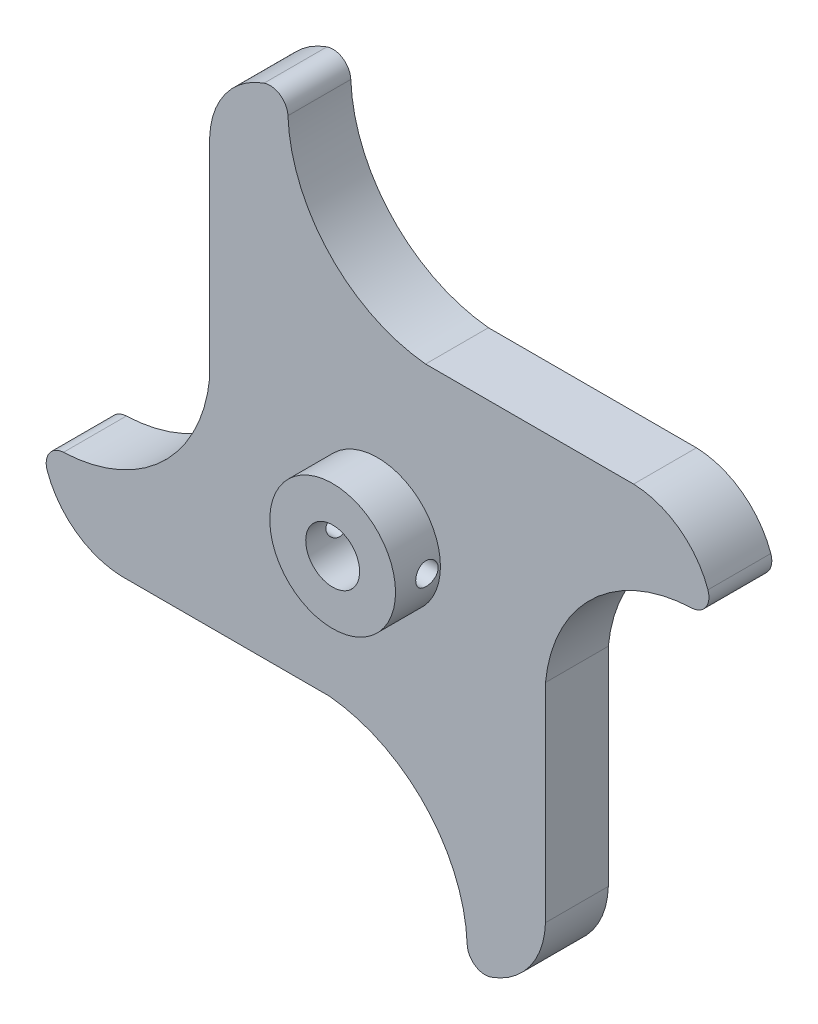
SolidWorks part; units mm, degrees
ref_plane "前视基准面" through (0, 0, 0) normal (0, 0, 1) x (1, 0, 0)
ref_plane "上视基准面" through (0, 0, 0) normal (0, 1, 0) x (1, 0, 0)
ref_plane "右视基准面" through (0, 0, 0) normal (1, 0, 0) x (0, 0, -1)
sketch "草图1" plane through (0, 0, 0) normal (0, 0, 1) x (1, 0, 0)
  circle A0 centre (0, 0) radius 3
  arc A5 (40.8798, 28.7896) -> (28.7896, 40.8798) centre (0, 0) ccw
  arc A7 (-28.7896, 40.8798) -> (-40.8798, 28.7896) centre (0, 0) ccw
  arc A9 (-40.8798, -28.7896) -> (-28.7896, -40.8798) centre (0, 0) ccw
  arc A11 (28.7896, -40.8798) -> (40.8798, -28.7896) centre (0, 0) ccw
  arc A13 (-22.8945, 32.8) -> (22.8945, 32.8) centre (0, 55.6945) ccw
  arc A14 (32.8, 22.8945) -> (32.8, -22.8945) centre (55.6945, 0) ccw
  arc A15 (22.8945, -32.8) -> (-22.8945, -32.8) centre (0, -55.6945) ccw
  arc A16 (-32.8, -22.8945) -> (-32.8, 22.8945) centre (-55.6945, 0) ccw
  arc A21 (-28.7896, 40.8798) -> (28.7896, 40.8798) centre (0, 55.6945) ccw
  arc A22 (40.8798, 28.7896) -> (40.8798, -28.7896) centre (55.6945, 0) ccw
  arc A23 (28.7896, -40.8798) -> (-28.7896, -40.8798) centre (0, -55.6945) ccw
  arc A24 (-40.8798, -28.7896) -> (-40.8798, 28.7896) centre (-55.6945, 0) ccw
  point P13 (45, 0)
  point P16 (0, 0)
  point P45 (0, 0)
  point P47 (0, 0)
  point P63 (0, 0)
  dimension "D3" = 4
  dimension "D4" = 4
extrude "凸台-拉伸1" add sketch "草图1" along normal blind 7 contours A24 A16 A9 A23 A15 A11 A22 A14 A5 A21 A13 A7 A0 region at (35.9294, 27.09, 0)
sketch "草图2" plane through (0, 0, 7) normal (0, 0, 1) x (1, 0, 0)
  line L0 (24.2343, 0) -> (24.2343, 20.8516)
  line L1 (0, -24.2343) -> (-200, -24.2343)
  line L2 (-200, -71.6) -> (3.2733, -71.6)
  line L3 (0, -70) -> (-200, -70)
  line L4 (-200, -23.4) -> (-200, -71.6)
  line L5 (24.2343, 34.0432) -> (24.2343, 20.8516)
  line L6 (-200, -47.5) -> (-20.9464, -47.5)
  line L7 (-200, -23.4) -> (-42.5285, -23.4)
  line L8 (70, 0) -> (70, 107.3223)
  line L9 (24.2343, 34.0432) -> (24.2343, 107.3223)
  line L10 (-35.8334, -17.6395) -> (24.2343, 34.0432)
  line L11 (24.2343, 34.0432) -> (-43.4982, -24.2343)
  line L12 (0, -24.2343) -> (0, 0)
  line L13 (0, 0) -> (0, -24.2343)
  line L14 (-43.4982, -24.2343) -> (-43.4982, -70)
  line L15 (-310.8913, -229.5208) -> (-198.8913, -229.5208)
  line L16 (-254.8913, -229.5208) -> (-251.3913, -229.5208)
  line L17 (-251.3913, -229.5208) -> (-258.3913, -229.5208)
  line L18 (-258.3913, -229.5208) -> (-258.3913, -112.5315)
  line L19 (-258.3913, -112.5315) -> (-251.3913, -112.5315)
  line L20 (-251.3913, -112.5315) -> (-251.3913, -229.5208)
  line L21 (24.2343, 107.3223) -> (70, 107.3223)
  line L22 (47.1172, 107.3223) -> (47.1172, -141.393)
  line L23 (-20.9464, -47.5) -> (114.3656, -47.5)
  line L24 (0, 0) -> (0, -24.2343)
  circle A0 centre (0, -49) radius 21
  circle A1 centre (-310.8913, -229.5208) radius 38.25
  arc A2 (0, -24.2343) -> (24.2343, 0) centre (0, 0) ccw
  arc A3 (0, -70) -> (70, 0) centre (0, 0) ccw
  circle A4 centre (-198.8913, -229.5208) radius 38.25
  circle A5 centre (0, 0) radius 47.1172
  circle A10 centre (-254.8913, -208.9571) radius 21.4063
  point P19 (0, 0)
sketch "草图5" plane through (0, 0, 7) normal (0, 0, 1) x (1, 0, 0)
  line L1 (0, 2.5) -> (-1.7806, 2.5)
  line L2 (-1.7806, 2.5) -> (1.6583, 2.5)
  arc A0 (1.6583, 2.5) -> (-1.6583, 2.5) centre (0, 0) ccw
  circle A1 centre (0, 0) radius 7
  circle M18 centre (0, 0) radius 3
extrude "凸台-拉伸2" add sketch "草图5" along normal blind 4 contours A1 M18 | L1 L2 M18 region at (0, 2.7015, 7) region at (-6.802, 0, 7)
sketch "草图10" plane through (0, 0, 7) normal (0, 0, -1) x (-1, 0, 0)
  line L0 (-1.6583, 2.5) -> (1.6583, 2.5) construction
  line L1 (-1.6583, 2.5) -> (1.6583, 2.5)
  arc A0 (-1.6583, 2.5) -> (1.6583, 2.5) centre (0, 0) cw
  arc A1 (1.6583, 2.5) -> (-1.6583, 2.5) centre (0, 0) ccw construction
extrude "凸台-拉伸3" add sketch "草图10" along normal up to surface (7 mm away) up to face at (0, 0, 0)
sketch "草图11" plane through (0, 0, 0) normal (1, 0, 0) x (0, 0, -1)
  line L0 (0, 0) -> (-7, 0)
  line L1 (-7, 0) -> (-10, 0)
  circle A0 centre (-8.5, 0) radius 1.25
extrude "切除-拉伸5" cut sketch "草图11" against normal blind 15 and the other way blind 8 contours L1 A0 | L1 A0 region at (0, -0.5305, 8.5) region at (0, 0.5305, 8.5)
sketch "草图12" plane through (0, 0, 11) normal (0, 0, 1) x (1, 0, 0)
  circle A0 centre (0, 0) radius 6
  circle A1 centre (0, 0) radius 3
extrude "凸台-拉伸4" add sketch "草图12" along normal blind 1
sketch "草图13" plane through (0, 0, 0) normal (0, 0, -1) x (-1, 0, 0)
  arc A0 (-25.2436, 31.0284) -> (25.2436, 31.0284) centre (0, 50.6945) ccw
  arc A1 (31.0284, 25.2436) -> (31.0284, -25.2436) centre (50.6945, 0) ccw
  arc A2 (25.2436, -31.0284) -> (-25.2436, -31.0284) centre (0, -50.6945) ccw
  arc A3 (-31.0284, -25.2436) -> (-31.0284, 25.2436) centre (-50.6945, 0) ccw
  arc A4 (-25.2436, 31.0284) -> (-31.0284, 25.2436) centre (0, 0) ccw
  circle A5 centre (0, 0) radius 82.6945
  arc A6 (-31.0284, -25.2436) -> (-25.2436, -31.0284) centre (0, 0) ccw
  arc A7 (25.2436, -31.0284) -> (31.0284, -25.2436) centre (0, 0) ccw
  arc A8 (31.0284, 25.2436) -> (25.2436, 31.0284) centre (0, 0) ccw
  point P14 (0, 0)
  dimension "D1" = 4
extrude "切除-拉伸13" cut sketch "草图13" against normal blind 10
fillet "圆角1" radius 2 4 edges at (-31.0284, -25.2436, 3.5) (31.0284, -25.2436, 3.5) (25.2436, 31.0284, 3.5) (-31.0284, 25.2436, 3.5)
fillet "圆角2" radius 2 4 edges at (-25.2436, -31.0284, 3.5) (25.2436, -31.0284, 3.5) (31.0284, 25.2436, 3.5) (-25.2436, 31.0284, 3.5)
sketch "草图14" plane through (0, 0, 0) normal (0, 0, -1) x (-1, 0, 0)
  line L0 (0, 18.6945) -> (-34.0956, 18.6945)
  line L1 (18.6945, 0) -> (18.6945, 34.0956)
  line L2 (0, -18.6945) -> (34.0956, -18.6945)
  line L3 (-18.6945, 0) -> (-18.6945, -34.0956)
  line L4 (34.0956, -16.9082) -> (34.0956, -18.6945)
  line L5 (-16.9082, -34.0956) -> (-18.6945, -34.0956)
  line L6 (-34.0956, 16.9082) -> (-34.0956, 18.6945)
  line L7 (16.9082, 34.0956) -> (18.6945, 34.0956)
  line L8 (13.8017, 34.0956) -> (18.6945, 34.0956)
  line L9 (34.0956, -13.8017) -> (34.0956, -18.6945)
  line L10 (-13.8017, -34.0956) -> (-18.6945, -34.0956)
  line L11 (-34.0956, 13.8017) -> (-34.0956, 18.6945)
  arc A1 (-23.9852, 29.5117) -> (23.9852, 29.5117) centre (0, 50.6945) ccw construction
  arc A5 (0, 18.6945) -> (13.8017, 34.0956) centre (-0.7997, 33.296) ccw
  arc A6 (18.6945, 0) -> (34.0956, -13.8017) centre (33.296, 0.7997) ccw
  arc A7 (0, -18.6945) -> (-13.8017, -34.0956) centre (0.7997, -33.296) ccw
  arc A8 (-18.6945, 0) -> (-34.0956, 13.8017) centre (-33.296, -0.7997) ccw
  point P22 (0, 0)
  point P29 (0, 0)
  point P35 (0, 0)
  point P41 (0, 0)
  arc M1 (-23.9852, -29.5117) -> (23.9852, -29.5117) centre (0, -50.6945) cw
  arc M5 (29.5117, -23.9852) -> (29.5117, 23.9852) centre (50.6945, 0) cw
  arc M9 (23.9852, 29.5117) -> (-23.9852, 29.5117) centre (0, 50.6945) cw
  arc M13 (-29.5117, 23.9852) -> (-29.5117, -23.9852) centre (-50.6945, 0) cw
  arc M17 (1.6583, 2.5) -> (-1.6583, 2.5) centre (0, 0) cw
  line M18 (-1.6583, 2.5) -> (1.6583, 2.5)
  dimension "D1" = 4
  dimension "D3" = 4
  dimension "D2" = 4
  dimension "D4" = 4
extrude "凸台-拉伸5" add sketch "草图14" against normal up to surface (7 mm away) contours L3 L2 L1 L0 M13 M1 M5 M9 M18 M17 | A8 L0 L6 L11 M13 | A5 L1 L7 L8 M9 | A6 L2 L4 L9 M5 | A7 L3 L5 L10 M1 region at (-10.0359, 19.5734, 0) region at (-14.1137, 26.53, 0) region at (26.53, 14.1137, 0) region at (-26.53, -14.1137, 0) region at (14.1137, -26.53, 0) up to face at (0, 0, 7)
sketch "草图15" plane through (0, 0, 0) normal (0, 0, -1) x (-1, 0, 0)
  line L0 (-24.7231, 18.6945) -> (0, 18.6945)
  line L1 (18.6945, 0) -> (18.6945, 24.7231)
  line L2 (24.7231, -18.6945) -> (0.9271, -18.708)
  line L3 (24.7231, -18.6945) -> (0, -18.6945)
  line L4 (18.6945, 24.7231) -> (18.6945, 0)
  line L5 (24.7231, -18.6945) -> (0, -18.6945)
  line L6 (-18.6945, -24.7231) -> (-18.6945, 0)
  line L7 (-18.6945, -24.7231) -> (-25.6921, -33.3347)
  line L8 (-25.6921, -33.3347) -> (-42.4976, -12.5302)
  line L9 (-42.4976, -12.5302) -> (-18.6945, 0)
  line L10 (-12.5302, 42.4976) -> (0, 18.6945)
  line L11 (-33.3347, 25.6921) -> (-12.5302, 42.4976)
  line L12 (-24.7231, 18.6945) -> (-33.3347, 25.6921)
  line L13 (42.4976, 12.5302) -> (18.6945, 0)
  line L14 (25.6921, 33.3347) -> (42.4976, 12.5302)
  line L15 (18.6945, 24.7231) -> (25.6921, 33.3347)
  line L16 (12.5302, -42.4976) -> (0, -18.6945)
  line L17 (33.3347, -25.6921) -> (12.5302, -42.4976)
  line L18 (24.7231, -18.6945) -> (33.3347, -25.6921)
  arc A0 (-23.9852, 29.5117) -> (0, 18.6945) centre (0, 50.6945) ccw construction
  arc A1 (0, 18.6945) -> (13.8017, 34.0956) centre (-0.7997, 33.296) ccw construction
  arc A2 (18.6945, 24.7231) -> (23.9852, 29.5117) centre (0, 50.6945) ccw construction
  arc A3 (23.9852, -29.5117) -> (0, -18.6945) centre (0, -50.6945) ccw construction
  point P35 (0, 0)
  point P47 (0, 0)
  arc M1 (-23.9852, -29.5117) -> (-18.6945, -24.7231) centre (0, -50.6945) cw
  arc M5 (0, -18.6945) -> (23.9852, -29.5117) centre (0, -50.6945) cw
  arc M6 (23.9852, -29.5117) -> (26.8255, -29.6714) centre (25.4843, -28.1878) ccw
  arc M7 (26.8255, -29.6714) -> (29.6714, -26.8255) centre (0, 0) ccw
  arc M8 (29.6714, -26.8255) -> (29.5117, -23.9852) centre (28.1878, -25.4843) ccw
  arc M9 (29.5117, -23.9852) -> (24.7231, -18.6945) centre (50.6945, 0) cw
  arc M13 (18.6945, 0) -> (29.5117, 23.9852) centre (50.6945, 0) cw
  arc M14 (29.5117, 23.9852) -> (29.6714, 26.8255) centre (28.1878, 25.4843) ccw
  arc M15 (29.6714, 26.8255) -> (26.8255, 29.6714) centre (0, 0) ccw
  arc M16 (26.8255, 29.6714) -> (23.9852, 29.5117) centre (25.4843, 28.1878) ccw
  arc M17 (23.9852, 29.5117) -> (18.6945, 24.7231) centre (0, 50.6945) cw
  arc M21 (0, 18.6945) -> (-23.9852, 29.5117) centre (0, 50.6945) cw
  arc M22 (-23.9852, 29.5117) -> (-26.8255, 29.6714) centre (-25.4843, 28.1878) ccw
  arc M23 (-26.8255, 29.6714) -> (-29.6714, 26.8255) centre (0, 0) ccw
  arc M24 (-29.6714, 26.8255) -> (-29.5117, 23.9852) centre (-28.1878, 25.4843) ccw
  arc M25 (-29.5117, 23.9852) -> (-24.7231, 18.6945) centre (-50.6945, 0) cw
  arc M29 (-18.6945, 0) -> (-29.5117, -23.9852) centre (-50.6945, 0) cw
  arc M30 (-29.5117, -23.9852) -> (-29.6714, -26.8255) centre (-28.1878, -25.4843) ccw
  arc M31 (-29.6714, -26.8255) -> (-26.8255, -29.6714) centre (0, 0) ccw
  arc M32 (-26.8255, -29.6714) -> (-23.9852, -29.5117) centre (-25.4843, -28.1878) ccw
  dimension "D1" = 4
  dimension "D2" = 4
extrude "切除-拉伸14" cut sketch "草图15" against normal blind 10 contours L12 L10 L11 M25 M24 M23 M22 M21 | L0 M25 M21 M22 M23 M24 | L1 M13 M14 M15 M16 M17 | L15 L13 L14 M17 M16 M15 M14 M13 | L2 M9 M5 M6 M7 M8 | L18 L16 L17 M9 M8 M7 M6 M5 | L9 L8 L7 M1 M32 M31 M30 M29 | L6 M1 M29 M30 M31 M32 region at (21.1855, 23.0093, 0) region at (14.0492, 29.1558, 0) region at (-29.1558, 14.0492, 0) region at (-23.0093, 21.1855, 0) region at (-21.2018, -23.0149, 0) region at (-14.0492, -29.1558, 0) region at (23.0093, -21.1855, 0) region at (29.1558, -14.0492, 0)
fillet "圆角3" radius 3 4 edges at (34.0956, 18.6945, 3.5) (18.6945, -34.0956, 3.5) (-34.0956, -18.6945, 3.5) (-18.6945, 34.0956, 3.5)
fillet "圆角4" radius 1 4 edges at (-34.0956, -13.8017, 3.5) (13.8017, -34.0956, 3.5) (34.0956, 13.8017, 3.5) (-13.8017, 34.0956, 3.5)
sketch "草图16" plane through (0, 0, 0) normal (0, 0, -1) x (-1, 0, 0)
  arc A0 (5.3467, -18.6945) -> (-9.9109, -37.2905) centre (7.0159, -35.6213) ccw
  arc A1 (-18.6945, -27.9842) -> (-9.9109, -37.2905) centre (-9.6496, -28.2455) ccw
  arc A2 (-18.6945, -5.3467) -> (-37.2905, 9.9109) centre (-35.6213, -7.0159) ccw
  arc A3 (-27.9842, 18.6945) -> (-37.2905, 9.9109) centre (-28.2455, 9.6496) ccw
  arc A4 (-5.3467, 18.6945) -> (9.9109, 37.2905) centre (-7.0159, 35.6213) ccw
  arc A5 (27.9842, -18.6945) -> (37.2905, -9.9109) centre (28.2455, -9.6496) ccw
  arc A6 (18.6945, 27.9842) -> (9.9109, 37.2905) centre (9.6496, 28.2455) ccw
  arc A9 (18.6945, 5.3467) -> (37.2905, -9.9109) centre (35.6213, 7.0159) ccw
  point P21 (0, 0)
  line M3 (34.0956, -15.6945) -> (34.0956, -14.8223)
  arc M4 (34.0956, -14.8223) -> (33.1085, -13.8224) centre (33.0956, -14.8223) ccw
  arc M5 (33.1085, -13.8224) -> (18.6945, 0) centre (33.296, 0.7997) cw
  line M6 (18.6945, 0) -> (18.6945, 31.0956)
  arc M7 (18.6945, 31.0956) -> (15.6945, 34.0956) centre (15.6945, 31.0956) ccw
  line M8 (15.6945, 34.0956) -> (14.8223, 34.0956)
  arc M9 (14.8223, 34.0956) -> (13.8224, 33.1085) centre (14.8223, 33.0956) ccw
  arc M10 (13.8224, 33.1085) -> (0, 18.6945) centre (-0.7997, 33.296) cw
  line M11 (0, 18.6945) -> (-31.0956, 18.6945)
  arc M12 (-31.0956, 18.6945) -> (-34.0956, 15.6945) centre (-31.0956, 15.6945) ccw
  line M13 (-34.0956, 15.6945) -> (-34.0956, 14.8223)
  arc M14 (-34.0956, 14.8223) -> (-33.1085, 13.8224) centre (-33.0956, 14.8223) ccw
  arc M15 (-33.1085, 13.8224) -> (-18.6945, 0) centre (-33.296, -0.7997) cw
  line M16 (-18.6945, 0) -> (-18.6945, -31.0956)
  arc M17 (-18.6945, -31.0956) -> (-15.6945, -34.0956) centre (-15.6945, -31.0956) ccw
  line M18 (-15.6945, -34.0956) -> (-14.8223, -34.0956)
  arc M19 (-14.8223, -34.0956) -> (-13.8224, -33.1085) centre (-14.8223, -33.0956) ccw
  arc M20 (-13.8224, -33.1085) -> (0, -18.6945) centre (0.7997, -33.296) cw
  arc M21 (0, -18.6945) -> (0.9271, -18.708) centre (0, -50.6945) cw
  line M22 (0.9271, -18.708) -> (24.7231, -18.6945)
  arc M24 (31.0956, -18.6945) -> (34.0956, -15.6945) centre (31.0956, -15.6945) ccw
  dimension "D1" = 4
sketch "草图17" plane through (0, 0, 7) normal (0, 0, 1) x (1, 0, 0)
  arc A0 (-18.6945, 27.9842) -> (-9.9109, 37.2905) centre (-9.6496, 28.2455) cw
  arc A1 (-9.9109, 37.2905) -> (5.3467, 18.6945) centre (7.0159, 35.6213) ccw
  arc A2 (37.2905, 9.9109) -> (18.6945, -5.3467) centre (35.6213, -7.0159) ccw
  arc A3 (27.9842, 18.6945) -> (37.2905, 9.9109) centre (28.2455, 9.6496) cw
  arc A4 (9.9109, -37.2905) -> (-5.3467, -18.6945) centre (-7.0159, -35.6213) ccw
  arc A5 (18.6945, -27.9842) -> (9.9109, -37.2905) centre (9.6496, -28.2455) cw
  arc A6 (-37.2905, -9.9109) -> (-18.6945, 5.3467) centre (-35.6213, 7.0159) ccw
  arc A7 (-27.9842, -18.6945) -> (-37.2905, -9.9109) centre (-28.2455, -9.6496) cw
  point P26 (0, 0)
  dimension "D1" = 4
extrude "凸台-拉伸6" add sketch "草图16" against normal up to surface (7 mm away) contours A6 A4 M7 M11 M10 M9 M8 | A3 A2 M12 M16 M15 M14 M13 | A1 A0 M17 M22 M21 M20 M19 M18 | A9 A5 M6 M5 M4 M3 M24 region at (-27.4674, -8.8381, 0) region at (-8.8381, 27.4674, 0) region at (27.4674, 8.8381, 0) region at (8.8457, -27.4731, 0) up to face at (-1.1659, -1.7, 7)
sketch "草图18" plane through (0, 0, 7) normal (0, 0, 1) x (1, 0, 0)
  line L0 (5.3467, 18.6945) -> (27.9842, 18.6945)
  line L1 (18.6945, -5.3467) -> (18.6945, -27.9842)
  line L2 (-5.3467, -18.6945) -> (-27.9842, -18.6945)
  line L3 (-18.6945, 5.3467) -> (-18.6945, 27.9842)
  arc A0 (-18.6945, 27.9842) -> (-9.9109, 37.2905) centre (-9.6496, 28.2455) cw
  arc A1 (-9.9109, 37.2905) -> (5.3467, 18.6945) centre (7.0159, 35.6213) ccw
  arc A2 (27.9842, 18.6945) -> (37.2905, 9.9109) centre (28.2455, 9.6496) cw
  arc A3 (37.2905, 9.9109) -> (18.6945, -5.3467) centre (35.6213, -7.0159) ccw
  arc A4 (18.6945, -27.9842) -> (9.9109, -37.2905) centre (9.6496, -28.2455) cw
  arc A5 (9.9109, -37.2905) -> (-5.3467, -18.6945) centre (-7.0159, -35.6213) ccw
  arc A6 (-27.9842, -18.6945) -> (-37.2905, -9.9109) centre (-28.2455, -9.6496) cw
  arc A7 (-37.2905, -9.9109) -> (-18.6945, 5.3467) centre (-35.6213, 7.0159) ccw
  circle A8 centre (0, 0) radius 47.2388
  point P31 (0, 0)
  dimension "D1" = 4
extrude "切除-拉伸15" cut sketch "草图18" against normal blind 10
fillet "圆角5" radius 2 4 edges at (-37.2905, -9.9109, 3.5) (9.9109, -37.2905, 3.5) (37.2905, 9.9109, 3.5) (-9.9109, 37.2905, 3.5)
sketch "草图19" plane through (0, 0, 7) normal (0, 0, 1) x (1, 0, 0)
  circle A0 centre (0, 0) radius 9.5
  circle A1 centre (9.5, 0) radius 3
extrude "切除-拉伸16" [suppressed] cut sketch "草图19" against normal blind 10 contours A0 A1 | A0 A1
sketch "草图22" plane through (0, 0, 11) normal (0, 0, 1) x (1, 0, 0)
  circle A0 centre (0, 0) radius 6
  circle A1 centre (0, 0) radius 7
extrude "凸台-拉伸8" add sketch "草图22" along normal up to surface (1 mm away) up to face at (6, 0, 12)
